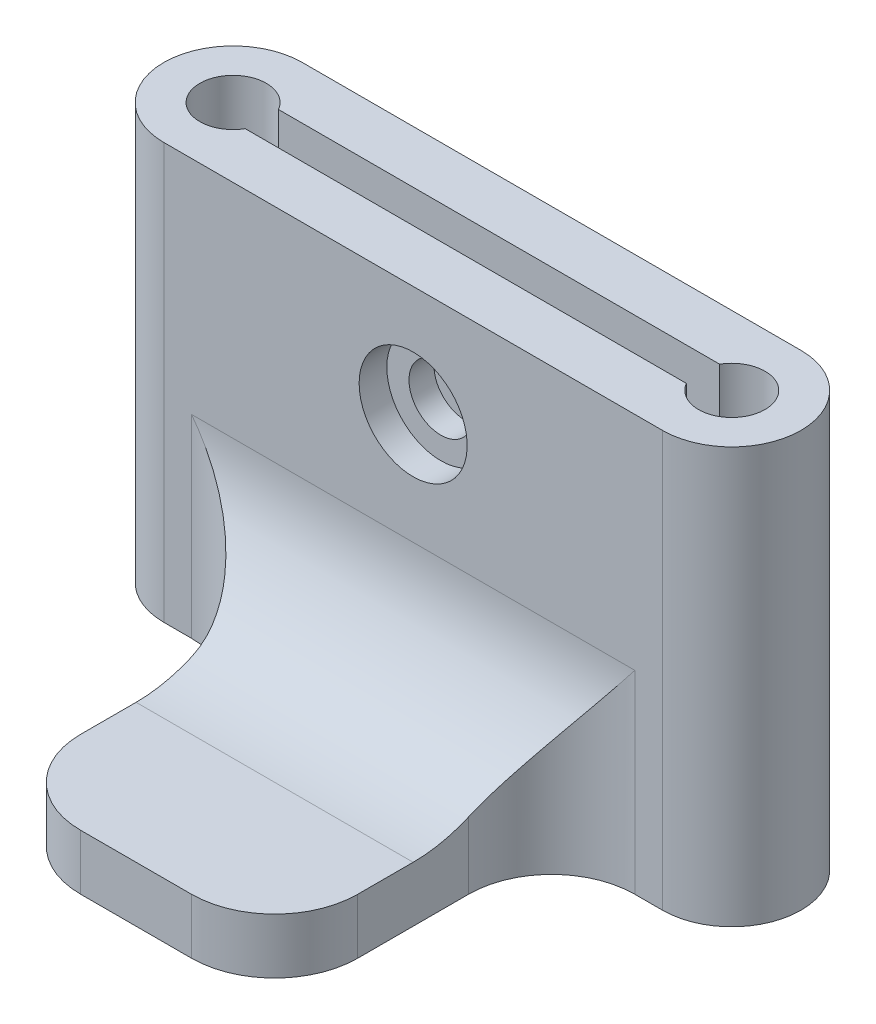
SolidWorks part; units mm, degrees
ref_plane "前视基准面" through (0, 0, 0) normal (0, 0, 1) x (1, 0, 0)
ref_plane "上视基准面" through (0, 0, 0) normal (0, 1, 0) x (1, 0, 0)
ref_plane "右视基准面" through (0, 0, 0) normal (1, 0, 0) x (0, 0, -1)
sketch "草图1" plane through (0, 0, 0) normal (0, 1, 0) x (1, 0, 0)
  line L0 (0, 0) -> (0, 4.7348) construction
  line L1 (0, 0) -> (9, 0) construction
  line L2 (-9, 0) -> (9, 0) construction
  line L3 (-6.4249, 17.0648) -> (6.4249, 17.0648) construction
  line L4 (-6.4249, 17.0648) -> (-6.4249, 3.25) construction
  line L5 (-6.4249, 3.25) -> (6.4249, 3.25) construction
  line L6 (6.4249, 17.0648) -> (6.4249, 3.25) construction
  line L7 (-6.4249, 17.0648) -> (6.4249, 3.25) construction
  line L8 (-6.4249, 3.25) -> (6.4249, 17.0648) construction
  line L9 (-9, 2.5) -> (9, 2.5)
  line L10 (-9, -2.5) -> (9, -2.5)
  circle A0 centre (0, 0) radius 11.5 construction
  circle A1 centre (9, 0) radius 1.2
  circle A2 centre (-9, 0) radius 1.2
  arc A3 (-9, 2.5) -> (-9, -2.5) centre (-9, 0) ccw
  arc A4 (9, -2.5) -> (9, 2.5) centre (9, 0) ccw
  point P8 (0, 10.1574)
  point P13 (0, 0)
  dimension "D1" = 23
  dimension "D3" = 2.4
  dimension "D2" = 18
  dimension "D4" = 3.25
extrude "凸台-拉伸1" add sketch "草图1" along normal blind 15
sketch "草图3" plane through (0, 0, 0) normal (0, -1, 0) x (1, 0, 0)
  line L0 (0, 0) -> (0, 5) construction
  line L1 (9, -2.5) -> (-9, -2.5) construction
  line L2 (-5, 12.5) -> (5, 12.5)
  line L3 (-5, 12.5) -> (-5, -2.5)
  line L4 (-5, -2.5) -> (5, -2.5)
  line L5 (5, 12.5) -> (5, -2.5)
  line L6 (-5, 12.5) -> (5, -2.5) construction
  line L7 (-5, -2.5) -> (5, 12.5) construction
  point P9 (3.9938, 10.5904)
  dimension "D1" = 10
  dimension "D2" = 15
extrude "凸台-拉伸2" add sketch "草图3" against normal blind 2
chamfer "倒角2" [suppressed] distance 10 angle 45
fillet "圆角2" radius 3 4 edges at (-5, 1, 12.5) (5, 1, 12.5) (5, 1, 2.5) (-5, 1, 2.5)
fillet "圆角3" radius 5 1 edges at (0, 2, 2.5)
sketch "草图4" plane through (0, 0, 0) normal (0, -1, 0) x (1, 0, 0)
  line L1 (-7.9608, -0.6) -> (7.9608, -0.6)
  line L2 (-7.9608, -0.6) -> (-7.9608, 0.6)
  line L3 (-7.9608, 0.6) -> (7.9608, 0.6)
  line L4 (7.9608, -0.6) -> (7.9608, 0.6)
  line L5 (-7.9608, -0.6) -> (7.9608, 0.6) construction
  line L6 (-7.9608, 0.6) -> (7.9608, -0.6) construction
  circle A0 centre (9, 0) radius 1.2 construction
  point P0 (0, 0)
  dimension "D1" = 1.2
extrude "切除-拉伸2" cut sketch "草图4" against normal through all
sketch "草图6" plane through (0, 0, 2.5) normal (0, 0, 1) x (1, 0, 0)
  line L0 (0, 0) -> (0, 11) construction
  line L1 (-9, 15) -> (9, 15) construction
  circle A0 centre (0, 11) radius 1.95
  point P4 (0, 6.0574)
  dimension "D1" = 3.9
  dimension "D2" = 4
extrude "切除-拉伸4" cut sketch "草图6" against normal blind 1 and the other way through all
sketch "草图7" plane through (0, 0, 1.5) normal (0, 0, 1) x (1, 0, 0)
  circle A0 centre (0, 11) radius 1.15
  dimension "D1" = 2.3
extrude "切除-拉伸5" cut sketch "草图7" against normal through all
sketch "草图8" plane through (0, 0, -2.5) normal (0, 0, -1) x (-1, 0, 0)
  line L0 (0, 13.4249) -> (0, 11) construction
  line L1 (0, 13.4249) -> (-2.1, 12.2124)
  line L2 (-2.1, 12.2124) -> (-2.1, 9.7876)
  line L3 (-2.1, 9.7876) -> (0, 8.5751)
  line L4 (0, 8.5751) -> (2.1, 9.7876)
  line L5 (2.1, 9.7876) -> (2.1, 12.2124)
  line L6 (2.1, 12.2124) -> (0, 13.4249)
  circle A0 centre (0, 11) radius 1.15 construction
  circle A1 centre (0, 11) radius 1.15 construction
  circle A2 centre (0, 11) radius 2.1 construction
  dimension "D1" = 4.2
extrude "切除-拉伸6" cut sketch "草图8" against normal blind 1
